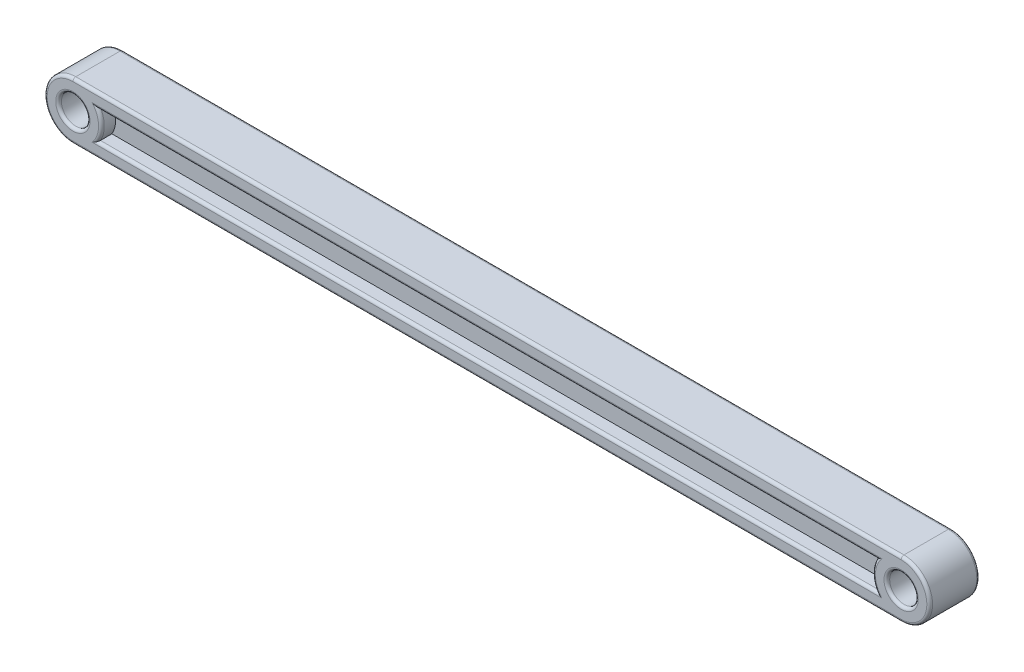
SolidWorks part; units mm, degrees
ref_plane "Front Plane" through (0, 0, 0) normal (0, 0, 1) x (1, 0, 0)
ref_plane "Top Plane" through (0, 0, 0) normal (0, 1, 0) x (1, 0, 0)
ref_plane "Right Plane" through (0, 0, 0) normal (1, 0, 0) x (0, 0, -1)
sketch "Sketch2" plane through (0, 0, 0) normal (0, 0, 1) x (1, 0, 0)
  line L0 (-290, 0) -> (290, 0) construction
  line L1 (-290, 20) -> (290, 20)
  line L2 (-290, -20) -> (290, -20)
  arc A0 (-290, 20) -> (-290, -20) centre (-290, 0) ccw
  arc A1 (290, -20) -> (290, 20) centre (290, 0) ccw
  circle A2 centre (-290, 0) radius 10
  circle A3 centre (290, 0) radius 10
  point P3 (0, 0)
  dimension "D1" = 580
  dimension "D2" = 20
  dimension "D3" = 20
extrude "Boss-Extrude1" add sketch "Sketch2" along normal mid plane 35
sketch "Sketch4" plane through (0, 0, -17.5) normal (0, 0, -1) x (-1, 0, 0)
  line L4 (290, 10) -> (-290, 10)
  line L5 (-290, -10) -> (290, -10)
  line L6 (272.6795, 10) -> (-272.6795, 10)
  line L7 (-272.6795, -10) -> (272.6795, -10)
  arc A4 (290, -10) -> (290, 10) centre (290, 0) ccw
  arc A5 (-290, 10) -> (-290, -10) centre (-290, 0) ccw
  circle A8 centre (-290, 0) radius 20
  arc A9 (-272.6795, -10) -> (-272.6795, 10) centre (-290, 0) ccw
  circle A11 centre (290, 0) radius 20
  arc A12 (272.6795, 10) -> (272.6795, -10) centre (290, 0) ccw
  dimension "D1" = 10
  dimension "D2" = 10
  dimension "D3" = 10
extrude "Cut-Extrude1" cut sketch "Sketch4" against normal blind 10
mirror "Mirror1" about plane through (0, 0, 0) normal (0, 0, 1) of "Cut-Extrude1"
fillet "Fillet4" radius 2 20 edges at (300, 0, -17.5) (300, 0, 17.5) (-280, 0, -17.5) (-280, 0, 17.5) (0, -10, 17.5) (-270, 0, 17.5) (0, 10, 17.5) (270, 0, 17.5) (-270, 0, -17.5) (0, -10, -17.5) (270, 0, -17.5) (0, 10, -17.5) (0, 20, 17.5) (310, 0, 17.5) (0, -20, 17.5) (-310, 0, 17.5) (0, -20, -17.5) (310, 0, -17.5) (0, 20, -17.5) (-310, 0, -17.5)
